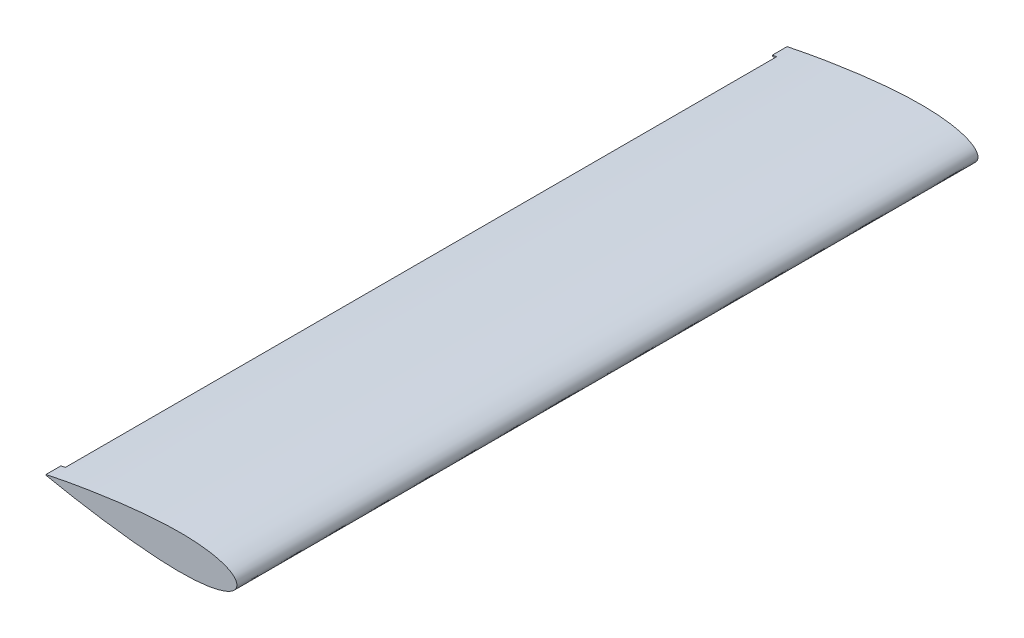
SolidWorks part; units mm, degrees
ref_plane "Alzado" through (0, 0, 0) normal (0, 0, 1) x (1, 0, 0)
ref_plane "Planta" through (0, 0, 0) normal (0, 1, 0) x (1, 0, 0)
ref_plane "Vista lateral" through (0, 0, 0) normal (1, 0, 0) x (0, 0, -1)
sketch "Croquis1" plane through (0, 0, 0) normal (0, 0, 1) x (1, 0, 0)
  line L0 (0, 0) -> (0, -23.5) construction
  line L1 (0, 0) -> (-16, 0) construction
  line L2 (-14.2698, -25.6618) -> (-26, -25.6618)
  line L3 (-26, -25.6618) -> (-26, -33.5)
  line L4 (-26, -33.5) -> (16, -33.5)
  line L5 (16, -33.5) -> (16, 3.8445)
  line L6 (16, 3.8445) -> (-14.2698, 3.8445)
  line L8 (-14.2698, -6.2762) -> (-14.2698, -25.6618)
  line L9 (-14.2698, 3.8445) -> (-26, 3.8445)
  line L10 (-26, 3.8445) -> (-26, -6.2762)
  line L11 (-26, -6.2762) -> (-14.2698, -6.2762)
  circle A0 centre (0, 0) radius 1.5
  dimension "D1" = 3
  dimension "D4" = 16
  dimension "D2" = 23.5
  dimension "D3" = 16
  dimension "D5" = 10
  dimension "D6" = 42
curve "Curva2"
  spline degree 3 poles (266, 0.503, 0) (261.5688, 1.4191, 0) (252.7164, 3.2493, 0) (234.9955, 6.6448, 0) (212.8433, 10.5485, 0) (186.2398, 14.7043, 0) (159.6407, 18.3128, 0) (133.0409, 21.2624, 0) (106.4348, 23.353, 0) (84.237, 24.0962, 0) (66.4893, 23.7999, 0) (53.1677, 23.0109, 0) (39.8211, 21.4881, 0) (28.7128, 19.3599, 0) (19.853, 16.8285, 0) (13.0874, 14.2708, 0) (7.4196, 11.1923, 0) (2.2073, 6.9321, 0) (-1.4404, 0, 0) (2.2073, -6.9321, 0) (7.4196, -11.1923, 0) (13.0874, -14.2708, 0) (19.853, -16.8285, 0) (28.7128, -19.3599, 0) (39.8211, -21.4881, 0) (53.1677, -23.0109, 0) (66.4893, -23.7999, 0) (84.237, -24.0962, 0) (106.4348, -23.353, 0) (133.0409, -21.2624, 0) (159.6407, -18.3128, 0) (186.2398, -14.7043, 0) (212.8433, -10.5485, 0) (234.9955, -6.6448, 0) (252.7164, -3.2493, 0) (261.5688, -1.4191, 0) (266, -0.503, 0) knots 0 0 0 0 0.024604 0.049152 0.098109 0.146905 0.195555 0.244056 0.292409 0.340644 0.364754 0.388905 0.413178 0.437756 0.450305 0.46323 0.477067 0.485036 0.5 0.514964 0.522933 0.53677 0.549695 0.562244 0.586822 0.611095 0.635246 0.659356 0.707591 0.755944 0.804445 0.853095 0.901891 0.950848 0.975396 1 1 1 1
sketch "Croquis6" plane through (0, 0, 0) normal (0, 0, 1) x (1, 0, 0)
  line L2 (-130.0015, 0) -> (0, 0) construction
  line L3 (-65.0007, 0) -> (-65.0007, 10.1736) construction
  line L4 (-128.8232, 0.2436) -> (-130.0015, 0)
  line L5 (-128.8232, -0.2436) -> (-130.0015, 0)
  spline S2 degree 3 poles (-128.8232, 0.2436) (-126.6771, 0.6873) (-122.39, 1.5736) (-113.8077, 3.2181) (-103.0795, 5.1086) (-90.1955, 7.1212) (-77.3136, 8.8689) (-64.4314, 10.2973) (-51.5461, 11.3098) (-40.7958, 11.6698) (-32.2006, 11.5262) (-25.749, 11.1441) (-19.2853, 10.4066) (-13.9056, 9.376) (-9.6147, 8.15) (-6.3382, 6.9113) (-3.5933, 5.4204) (-1.069, 3.3572) (0.6976, 0) (-1.069, -3.3572) (-3.5933, -5.4204) (-6.3382, -6.9113) (-9.6147, -8.15) (-13.9056, -9.376) (-19.2853, -10.4066) (-25.749, -11.1441) (-32.2006, -11.5262) (-40.7958, -11.6698) (-51.5461, -11.3098) (-64.4314, -10.2973) (-77.3136, -8.8689) (-90.1955, -7.1212) (-103.0795, -5.1086) (-113.8077, -3.2181) (-122.39, -1.5736) (-126.6771, -0.6873) (-128.8232, -0.2436) knots 0 0 0 0 0.024604 0.049152 0.098109 0.146905 0.195555 0.244056 0.292409 0.340644 0.364754 0.388905 0.413178 0.437756 0.450305 0.46323 0.477067 0.485036 0.5 0.514964 0.522933 0.53677 0.549695 0.562244 0.586822 0.611095 0.635246 0.659356 0.707591 0.755944 0.804445 0.853095 0.901891 0.950848 0.975396 1 1 1 1
  point P8 (0, 0)
  dimension "D1" = 130.0015
sketch "Croquis7" plane through (0, 0, 0) normal (0, 0, 1) x (1, 0, 0)
  line L0 (-128.8232, 0.2436) -> (-130.0015, 0) construction
  line L1 (-128.8232, 0.2436) -> (-130.0015, 0) construction
  line L2 (-128.8232, -0.2436) -> (-130.0015, 0) construction
  line L3 (-128.8232, -0.2436) -> (-130.0015, 0) construction
  line L4 (-128.8232, -0.2436) -> (-128.8232, 0.2436)
  spline S0 degree 3 poles (-835.2568, 1861.3988) (-332.4561, -82.1992) (-229.4715, -18.9446) (-113.8077, 3.2181) (-103.0795, 5.1086) (-90.1955, 7.1212) (-77.3136, 8.8689) (-64.4314, 10.2973) (-51.5461, 11.3098) (-40.7958, 11.6698) (-32.2006, 11.5262) (-25.749, 11.1441) (-19.2853, 10.4066) (-13.9056, 9.376) (-9.6147, 8.15) (-6.3382, 6.9113) (-3.5933, 5.4204) (-1.069, 3.3572) (0.6976, 0) (-1.069, -3.3572) (-3.5933, -5.4204) (-6.3382, -6.9113) (-9.6147, -8.15) (-13.9056, -9.376) (-19.2853, -10.4066) (-25.749, -11.1441) (-32.2006, -11.5262) (-40.7958, -11.6698) (-51.5461, -11.3098) (-64.4314, -10.2973) (-77.3136, -8.8689) (-90.1955, -7.1212) (-103.0795, -5.1086) (-113.8077, -3.2181) (-229.4717, 18.9446) (-332.4565, 82.1995) (-835.2603, -1861.4125) knots -1.224113 -1.224113 -1.224113 -1.224113 0.024604 0.049152 0.098109 0.146905 0.195555 0.244056 0.292409 0.340644 0.364754 0.388905 0.413178 0.437756 0.450305 0.46323 0.477067 0.485036 0.5 0.514964 0.522933 0.53677 0.549695 0.562244 0.586822 0.611095 0.635246 0.659356 0.707591 0.755944 0.804445 0.853095 0.901891 0.950848 0.975396 2.224116 2.224116 2.224116 2.224116 only from (-128.8232, 0.2436) to (-128.8232, -0.2436) construction
  spline S1 degree 3 poles (-128.8232, 0.2436) (-126.6771, 0.6873) (-122.39, 1.5736) (-113.8077, 3.2181) (-103.0795, 5.1086) (-90.1955, 7.1212) (-77.3136, 8.8689) (-64.4314, 10.2973) (-51.5461, 11.3098) (-40.7958, 11.6698) (-32.2006, 11.5262) (-25.749, 11.1441) (-19.2853, 10.4066) (-13.9056, 9.376) (-9.6147, 8.15) (-6.3382, 6.9113) (-3.5933, 5.4204) (-1.069, 3.3572) (0.6976, 0) (-1.069, -3.3572) (-3.5933, -5.4204) (-6.3382, -6.9113) (-9.6147, -8.15) (-13.9056, -9.376) (-19.2853, -10.4066) (-25.749, -11.1441) (-32.2006, -11.5262) (-40.7958, -11.6698) (-51.5461, -11.3098) (-64.4314, -10.2973) (-77.3136, -8.8689) (-90.1955, -7.1212) (-103.0795, -5.1086) (-113.8077, -3.2181) (-122.39, -1.5736) (-126.6771, -0.6873) (-128.8232, -0.2436) knots 0 0 0 0 0.024604 0.049152 0.098109 0.146905 0.195555 0.244056 0.292409 0.340644 0.364754 0.388905 0.413178 0.437756 0.450305 0.46323 0.477067 0.485036 0.5 0.514964 0.522933 0.53677 0.549695 0.562244 0.586822 0.611095 0.635246 0.659356 0.707591 0.755944 0.804445 0.853095 0.901891 0.950848 0.975396 1 1 1 1
extrude "Saliente-Extruir1" add sketch "Croquis7" along normal mid plane 500
sketch "Croquis8" plane through (0, 0, 0) normal (0, 0, 1) x (1, 0, 0)
  line L0 (-128.9842, -0.6178) -> (-128.9842, 0.6178)
  line L2 (-125.8047, -1.25) -> (-125.8047, 1.25)
  line L4 (-128.8232, 0.2436) -> (-128.8232, -0.2436) construction
  line L5 (-125.8047, 1.25) -> (-128.9842, 0.6178)
  line L6 (-128.9842, -0.6178) -> (-125.8047, -1.25)
  line L7 (-130.0015, 0) -> (0, 0) construction
  point P3 (-128.9842, 0)
  point P6 (-125.8047, 0)
  dimension "D1" = 3.0184
  dimension "D2" = 2.5
extrude "Cortar-Extruir1" cut sketch "Croquis8" against normal mid plane 480
